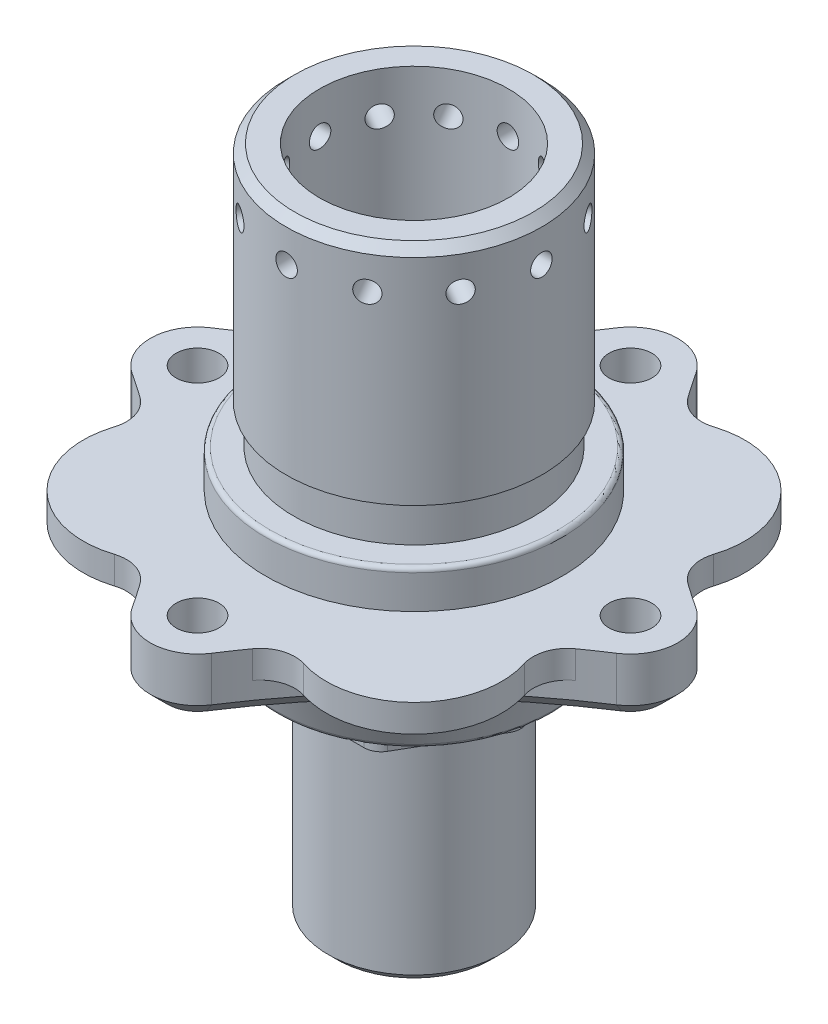
SolidWorks part; units mm, degrees
material "7075-T6 (SN)"
ref_plane "X-Y Datum" through (0, 0, 0) normal (0, 0, 1) x (1, 0, 0)
ref_plane "X-Z Datum" through (0, 0, 0) normal (0, 1, 0) x (1, 0, 0)
ref_plane "Y-Z Datum" through (0, 0, 0) normal (1, 0, 0) x (0, 0, -1)
sketch "Sketch1" plane through (0, 0, 0) normal (1, 0, 0) x (0, 0, -1)
  line L0 (0, 0) -> (-50000, 0) construction
  line L1 (0, 0) -> (0, 50000) construction
  line L2 (0, 0) -> (-29.4793, 0)
  line L3 (-29.4793, 0) -> (-25.0825, -12.0802)
  line L4 (-25.0825, -12.0802) -> (-25.0825, -16.8427)
  line L5 (-25.0825, -16.8427) -> (-15.8877, -16.8427)
  line L8 (0, -56.4667) -> (0, 0)
  line L9 (0, -56.4667) -> (-14.3002, -56.4667)
  line L10 (-15.8877, -16.8427) -> (-15.8877, -54.8792)
  line L11 (-14.3002, -56.4667) -> (-15.8877, -54.8792)
  dimension "D1" = 56.4667
  dimension "D2" = 4.7625
  dimension "D3" = 39.624
  dimension "D4" = 50.165
  dimension "D5" = 45
  dimension "D6" = 70
  dimension "D7" = 31.7754
  dimension "D8" = 1.5875
sketch "Sketch2" plane through (0, 0, 0) normal (1, 0, 0) x (0, 0, -1)
  line L0 (0, 0) -> (-52.3875, 0)
  line L1 (200000, 0) -> (-250000, 0) construction
  line L2 (-52.3875, 0) -> (-52.3875, 11.43)
  line L3 (-52.3875, 11.43) -> (-27.4096, 11.43)
  line L4 (-27.4096, 11.43) -> (-27.4096, 18.43)
  line L5 (-27.4096, 18.43) -> (-22.225, 18.43)
  line L6 (-22.225, 18.43) -> (-22.225, 25.7175)
  line L7 (-22.225, 25.7175) -> (-23.6195, 25.7175)
  line L10 (0, -200000) -> (0, 250000) construction
  line L11 (0, 66.9925) -> (0, 0)
  line L15 (0, 66.9925) -> (-22.032, 66.9925)
  line L16 (-22.032, 66.9925) -> (-23.6195, 65.405)
  line L17 (-23.6195, 65.405) -> (-23.6195, 25.7175)
  line L18 (0, 0) -> (-50000, 0) construction
  line L19 (0, 0) -> (0, 50000) construction
  line L20 (0, 0) -> (0, -31242.0183) construction
  dimension "D1" = 11.43
  dimension "D2" = 55.5625
  dimension "D3" = 47.2389
  dimension "D4" = 1.5875
  dimension "D5" = 45
  dimension "D6" = 54.8192
  dimension "D7" = 104.775
  dimension "D8" = 7
  dimension "D9" = 39.6875
  dimension "D10" = 44.45
revolve "Bearing Shaft/Flange Support" add sketch "Sketch1" angle 360 about L1
revolve "Drive Pin Support" add sketch "Sketch2" angle 360 about L19
sketch "Sketch5" plane through (0, 0, 0) normal (1, 0, 0) x (0, 0, -1)
  line L0 (0, 66.9925) -> (17.4625, 66.9925)
  line L1 (22.032, 66.9925) -> (-22.032, 66.9925) construction
  line L2 (17.4625, 66.9925) -> (17.4625, 19.3675)
  line L3 (17.4625, 19.3675) -> (12.7, -12.3825)
  line L4 (12.7, -12.3825) -> (0, -12.3825)
  line L5 (0, -12.3825) -> (0, 66.9925)
  line L6 (0, 0) -> (-50000, 0) construction
  line L8 (0, 0) -> (0, -50000) construction
  dimension "D1" = 79.375
  dimension "D2" = 47.625
  dimension "D3" = 34.925
  dimension "D4" = 25.4
revolve "Center Mass Removal" cut sketch "Sketch5" angle 360 about L8
hole_wizard "Drive Pin Holes" positions "Sketch6" profile "Sketch7" tap size "3/8-16" standard "ANSI Inch" end condition through all
sketch "Sketch6" plane through (0, 0, 0) normal (0, -1, 0) x (-1, 0, 0)
  circle A0 centre (0, 0) radius 40 construction
  point P0 (0, -40)
  dimension "D1" = 80
sketch "Sketch7" plane through (0, 0, 40) normal (1, 0, 0) x (0, 0, -1)
  line L0 (0, 0) -> (0, 66.9925)
  line L1 (0, 66.9925) -> (3.9687, 66.9925)
  line L2 (3.9687, 66.9925) -> (3.9687, 0)
  line L5 (3.9687, 0) -> (0, 0)
  line L11 (0, -6.35) -> (0, 107.95) construction
  dimension "Thru Tap Drill Dia." = 7.9375
  dimension "Thru Tap Drill Depth" = 66.9925
cosmetic thread "Hole Thread1" parameters "D2"=9.525
pattern_circular "Drive Pin Holes Pattern" count 4 over 360 about axis through (0, 0, 0) along (0, 1, 0) of "Drive Pin Holes"
cosmetic thread "Hole Thread2" parameters "D2"=9.525
cosmetic thread "Hole Thread3" parameters "D2"=9.525
cosmetic thread "Hole Thread4" parameters "D2"=9.525
sketch "Sketch8" plane through (0, 0, 0) normal (0, -1, 0) x (1, 0, 0)
  arc A0 (7.3249, 44.7518) -> (-7.3249, 44.7518) centre (0, 40) ccw
  arc A1 (7.3249, 44.7518) -> (44.7518, 7.3249) centre (113.8695, 113.8695) ccw
  arc A2 (44.7518, -7.3249) -> (44.7518, 7.3249) centre (40, 0) ccw
  arc A3 (44.7518, -7.3249) -> (44.7518, 7.3249) centre (40, 0) ccw
  arc A5 (44.7518, -7.3249) -> (7.3249, -44.7518) centre (113.8695, -113.8695) ccw
  circle A7 centre (0, 40) radius 3.9687 construction
  circle A8 centre (0, 0) radius 52.3875 construction
  circle A9 centre (0, 0) radius 40 construction
  arc A10 (-7.3249, -44.7518) -> (7.3249, -44.7518) centre (0, -40) ccw
  arc A11 (-7.3249, -44.7518) -> (7.3249, -44.7518) centre (0, -40) ccw
  arc A13 (-44.7518, 7.3249) -> (-44.7518, -7.3249) centre (-40, 0) ccw
  arc A14 (-44.7518, 7.3249) -> (-44.7518, -7.3249) centre (-40, 0) ccw
  arc A15 (-44.7518, 7.3249) -> (-7.3249, 44.7518) centre (-113.8695, 113.8695) ccw
  arc A16 (7.3249, 44.7518) -> (-7.3249, 44.7518) centre (0, 40) ccw
  circle A17 centre (0, 0) radius 52.3875
  arc A18 (-7.3249, -44.7518) -> (-44.7518, -7.3249) centre (-113.8695, -113.8695) ccw
  arc A19 (-170.1077, 0) -> (0, -170.1077) centre (-113.8695, -113.8695) ccw [skipped]
  circle M10 centre (0, 0) radius 52.3875
  dimension "D1" = 4.7625
  dimension "D3" = 254
  dimension "D4" = 80
  dimension "D5" = 4
extrude "Flange Support Cut" cut sketch "Sketch8" against normal blind 6.35 contours A10 A18 A13 A15 A0 A1 A2 A5 M10
sketch "Sketch9" plane through (0, 6.35, 0) normal (0, -1, 0) x (1, 0, 0)
  line L0 (0, 0) -> (0, 50000) construction
  line L1 (0, 0) -> (50000, 0) construction
  line L2 (0, 0) -> (-35355.3391, 35355.3391) construction
  arc A0 (-44.7518, 7.3249) -> (-44.7518, -7.3249) centre (-40, 0) ccw construction
  arc A1 (-7.3249, -44.7518) -> (-44.7518, -7.3249) centre (-113.8695, -113.8695) ccw construction
  arc A2 (-7.3249, -44.7518) -> (7.3249, -44.7518) centre (0, -40) ccw construction
  arc A3 (44.7518, -7.3249) -> (7.3249, -44.7518) centre (113.8695, -113.8695) ccw construction
  arc A4 (44.7518, -7.3249) -> (44.7518, 7.3249) centre (40, 0) ccw construction
  arc A5 (7.3249, 44.7518) -> (44.7518, 7.3249) centre (113.8695, 113.8695) ccw construction
  arc A6 (7.3249, 44.7518) -> (-7.3249, 44.7518) centre (0, 40) ccw construction
  arc A7 (-44.7518, 7.3249) -> (-7.3249, 44.7518) centre (-113.8695, 113.8695) ccw construction
  arc A8 (-44.7518, 7.3249) -> (-44.7518, -7.3249) centre (-40, 0) ccw
  arc A9 (-7.3249, -44.7518) -> (-13.546, -35.9966) centre (-113.8695, -113.8695) ccw
  arc A10 (-7.3249, -44.7518) -> (7.3249, -44.7518) centre (0, -40) ccw
  arc A11 (44.7518, -7.3249) -> (35.9966, -13.546) centre (113.8695, -113.8695) ccw
  arc A12 (44.7518, -7.3249) -> (44.7518, 7.3249) centre (40, 0) ccw
  arc A13 (7.3249, 44.7518) -> (13.546, 35.9966) centre (113.8695, 113.8695) ccw
  arc A14 (7.3249, 44.7518) -> (-7.3249, 44.7518) centre (0, 40) ccw
  arc A15 (-44.7518, 7.3249) -> (-35.9966, 13.546) centre (-113.8695, 113.8695) ccw
  arc A16 (-35.9966, 13.546) -> (-13.546, 35.9966) centre (-22.4506, 22.4506) cw
  arc A17 (13.546, 35.9966) -> (35.9966, 13.546) centre (22.4506, 22.4506) cw
  arc A18 (35.9966, -13.546) -> (13.546, -35.9966) centre (22.4506, -22.4506) cw
  arc A19 (-13.546, -35.9966) -> (-35.9966, -13.546) centre (-22.4506, -22.4506) cw
  arc A20 (35.9966, 13.546) -> (44.7518, 7.3249) centre (113.8695, 113.8695) ccw
  arc A21 (-13.546, 35.9966) -> (-7.3249, 44.7518) centre (-113.8695, 113.8695) ccw
  arc A22 (13.546, -35.9966) -> (7.3249, -44.7518) centre (113.8695, -113.8695) ccw
  arc A23 (-35.9966, -13.546) -> (-44.7518, -7.3249) centre (-113.8695, -113.8695) ccw
  circle M11 centre (0, 0) radius 52.3875
  arc M12 (7.3249, -44.7518) -> (-7.3249, -44.7518) centre (0, -40) cw
  arc M13 (-7.3249, -44.7518) -> (-44.7518, -7.3249) centre (-113.8695, -113.8695) ccw
  arc M14 (-44.7518, -7.3249) -> (-44.7518, 7.3249) centre (-40, 0) cw
  arc M15 (-44.7518, 7.3249) -> (-7.3249, 44.7518) centre (-113.8695, 113.8695) ccw
  arc M16 (-7.3249, 44.7518) -> (7.3249, 44.7518) centre (0, 40) cw
  arc M17 (7.3249, 44.7518) -> (44.7518, 7.3249) centre (113.8695, 113.8695) ccw
  arc M18 (44.7518, 7.3249) -> (44.7518, -7.3249) centre (40, 0) cw
  arc M19 (44.7518, -7.3249) -> (7.3249, -44.7518) centre (113.8695, -113.8695) ccw
  dimension "D1" = 45
  dimension "D2" = 31.75
  dimension "D3" = 31.75
  dimension "D4" = 4
extrude "Floral Pattern Cut" cut sketch "Sketch9" against normal through all contours A19 A16 A17 A18 M11 M13 M14 M15 M16 M17 M18 M19 M12
sketch "Sketch10" plane through (0, -16.8427, 0) normal (0, -1, 0) x (1, 0, 0)
  line L0 (0, 0) -> (0, 50000) construction
  line L1 (10.1025, -17.4981) -> (20.205, 0)
  line L2 (20.205, 0) -> (10.1025, 17.4981)
  line L3 (10.1025, 17.4981) -> (-10.1025, 17.4981)
  line L4 (-10.1025, 17.4981) -> (-20.205, 0)
  line L5 (-20.205, 0) -> (-10.1025, -17.4981)
  line L6 (-10.1025, -17.4981) -> (10.1025, -17.4981)
  line L7 (0, 0) -> (50000, 0) construction
  circle A0 centre (0, 0) radius 17.4981 construction
  circle A1 centre (0, 0) radius 25.0825 construction
  circle A2 centre (0, 0) radius 25.0825
  point P17 (0, 17.4981)
  dimension "D1" = 34.9961
extrude "Brake Hat Hex" cut sketch "Sketch10" against normal blind 4.7625
sketch "Sketch11" plane through (0, -56.4667, 0) normal (0, -1, 0) x (1, 0, 0)
  circle A25 centre (0, 0) radius 9.525 construction
  circle A26 centre (0, 9.525) radius 3.175
  circle A27 centre (8.2489, 4.7625) radius 3.175
  circle A28 centre (8.2489, -4.7625) radius 3.175
  circle A29 centre (0, -9.525) radius 3.175
  circle A30 centre (-8.2489, -4.7625) radius 3.175
  circle A31 centre (-8.2489, 4.7625) radius 3.175
  dimension "D1" = 19.05
  dimension "D2" = 6.35
  dimension "D3" = 6
hole_wizard "5/16 Clearance Hole1" positions "Sketch12" profile "Sketch13" hole size "5/16" standard "ANSI Inch" end condition through all
sketch "Sketch12" plane through (0, -56.4667, 0) normal (0, -1, 0) x (-1, 0, 0)
  point P0 (0, 0)
sketch "Sketch13" plane through (0, -56.4667, 0) normal (1, 0, 0) x (0, 0, -1)
  line L0 (0, 0) -> (0, 123.4592)
  line L1 (0, 123.4592) -> (4.1021, 123.4592)
  line L2 (4.1021, 123.4592) -> (4.1021, 0)
  line L5 (4.1021, 0) -> (0, 0)
  line L11 (0, -6.35) -> (0, 107.95) construction
  dimension "Thru Hole Dia." = 8.2042
  dimension "Thru Hole Depth" = 123.4592
fillet "Brake Hat Fillet" radius 3.175 6 edges at (20.205, -14.4615, 0) (10.1025, -14.4615, 17.4981) (-10.1025, -14.4615, 17.4981) (-20.205, -14.4615, 0) (-10.1025, -14.4615, -17.4981) (10.1025, -14.4615, -17.4981)
fillet "Hub Fillet" radius 0.7937 1 edges at (0, 18.43, -27.4096)
sketch "Sketch14" plane through (0, 0, 0) normal (1, 0, 0) x (0, 0, -1)
  line L0 (17.4625, 66.9925) -> (-17.4625, 66.9925) construction
  line L1 (0, 0) -> (-50000, 0) construction
  line L2 (0, 0) -> (0, -50000) construction
  circle A0 centre (0, 59.3725) radius 1.9844
  dimension "D2" = 3.9688
  dimension "D1" = 7.62
extrude "Pin Holes" cut sketch "Sketch14" against normal through all
pattern_circular "Pin Hole Pattern" count 12 over 360 about axis through (0, 66.9925, 0) along (0, 1, 0) of "Pin Holes"
chamfer "Floral Pattern Chamfer" distance 3.175 angle 45 8 edges at (0, 0, -48.7312) (24.067, 0, -24.067) (48.7312, 0, 0) (-24.067, 0, -24.067) (-48.7312, 0, 0) (-24.067, 0, 24.067) (0, 0, 48.7313) (24.067, 0, 24.067)
fillet "Floral Pattern Fillet" radius 6.35 8 edges at (-35.9966, 8.89, 13.546) (-13.546, 8.89, 35.9966) (-35.9966, 8.89, -13.546) (-13.546, 8.89, -35.9966) (13.546, 8.89, -35.9966) (35.9966, 8.89, -13.546) (35.9966, 8.89, 13.546) (13.546, 8.89, 35.9966)
sketch3d "3DSketch2"
  line L0 (0, 0, 0) -> (0, 0, -205.74)
  line L1 (0, 0, -205.74) -> (25.4, 0, -205.74)
  line L2 (0, 0, -205.74) -> (0, -25.4, -205.74)
  dimension "D1" = 25.4
  dimension "D2" = 25.4
  dimension "D3" = 205.74
extrude "Tripod Pins" [suppressed] cut sketch "Sketch11" against normal blind 12.7
fillet "Flange Fillet" radius 1.27 1 edges at (0, -12.0802, -25.0825)
sketch "Sketch15" plane through (0, 0, 0) normal (0, -1, 0) x (1, 0, 0)
  circle A0 centre (0, 0) radius 40 construction
  dimension "D1" = 80
thread "Thread1" [suppressed] pitch 2.1167 start angle 0, offset 0.3048, length 0, pitch 2.1167, diameter 47.625
ref_plane "Plane1" through (-23.8125, 67.2973, 0) normal (0, 0, 1) x (-1, 0, 0)
sketch "Thread Profile1" plane through (-23.8125, 67.2973, 0) normal (0, 0, 1) x (-1, 0, 0)
  line L0 (0, 0) -> (0, 2.1167) construction
  line L11 (0, 0) -> (0, 1.8521)
  line L12 (0, 1.8521) -> (-1.1457, 1.1906)
  line L13 (-1.1457, 1.1906) -> (-1.1457, 0.6615)
  line L15 (-1.1457, 0.6615) -> (0, 0)
  line L17 (-1.1457, 0.926) -> (0, 0.926) construction
  point P2 (0, 0)
  dimension "Pitch" = 2.1167
  dimension "Profile_Angle" = 60
  dimension "Profile_Land" = 0.5292
  dimension "Profile_Height" = 1.1457
sketch "Sketch17" plane through (0, -56.4667, 0) normal (0, -1, 0) x (1, 0, 0)
  line L7 (5.4993, 9.525) -> (-5.4993, 9.525)
  line L8 (-5.4993, 9.525) -> (-10.9985, 0)
  line L9 (-10.9985, 0) -> (-5.4993, -9.525)
  line L10 (-5.4993, -9.525) -> (5.4993, -9.525)
  line L11 (5.4993, -9.525) -> (10.9985, 0)
  line L12 (10.9985, 0) -> (5.4993, 9.525)
  circle A0 centre (0, 0) radius 9.525 construction
  dimension "D1" = 19.05
extrude "Cut-Extrude1" cut sketch "Sketch17" against normal blind 12.954
fillet "Fillet1" radius 3.175 6 edges at (-5.4993, -49.9897, -9.525) (5.4993, -49.9897, -9.525) (10.9985, -49.9897, 0) (5.4993, -49.9897, 9.525) (-5.4993, -49.9897, 9.525) (-10.9985, -49.9897, 0)
